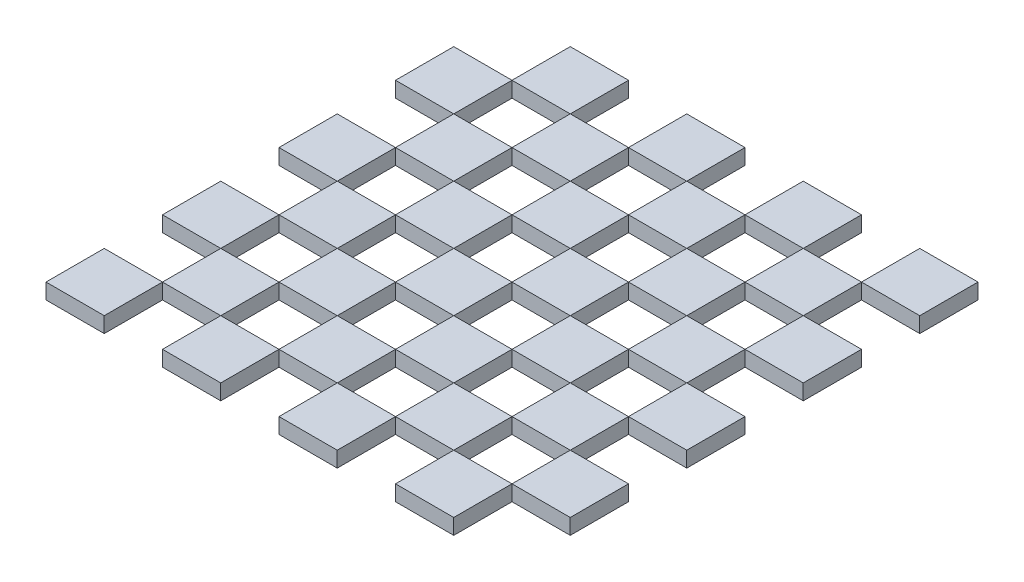
SolidWorks part; units mm, degrees
material "Plain Carbon Steel"
ref_plane "Front Plane" through (0, 0, 0) normal (0, 0, 1) x (1, 0, 0)
ref_plane "Top Plane" through (0, 0, 0) normal (0, 1, 0) x (1, 0, 0)
ref_plane "Right Plane" through (0, 0, 0) normal (1, 0, 0) x (0, 0, -1)
sketch "Sketch1" plane through (0, 0, 0) normal (0, 1, 0) x (1, 0, 0)
  line L0 (0, 150) -> (0, -150)
  line L1 (-150, -150) -> (150, -150)
  line L2 (-150, -150) -> (-150, 150)
  line L3 (-150, 150) -> (150, 150)
  line L4 (150, -150) -> (150, 150)
  line L5 (-150, -150) -> (150, 150) construction
  line L6 (-150, 150) -> (150, -150) construction
  line L7 (-112.5, 150) -> (-112.5, -150)
  line L8 (37.5, 150) -> (37.5, -150)
  line L9 (-75, 150) -> (-75, -150)
  line L10 (-37.5, 150) -> (-37.5, -150)
  line L11 (75, 150) -> (75, -150)
  line L12 (112.5, 150) -> (112.5, -150)
  line L13 (-150, -75) -> (150, -75)
  line L14 (-150, 37.5) -> (150, 37.5)
  line L15 (-150, 75) -> (150, 75)
  line L16 (-150, -112.5) -> (150, -112.5)
  line L17 (-150, 0) -> (150, 0)
  line L18 (-150, -37.5) -> (150, -37.5)
  line L19 (-150, 112.5) -> (150, 112.5)
  point P0 (0, 0)
  point P20 (0, 0)
  dimension "D1" = 300
  dimension "D2" = 37.5
  dimension "D3" = 37.5
  dimension "D4" = 37.5
  dimension "D5" = 37.5
  dimension "D6" = 37.5
  dimension "D7" = 37.5
  dimension "D8" = 37.5
  dimension "D9" = 37.5
  dimension "D10" = 37.5
  dimension "D11" = 37.5
  dimension "D12" = 37.5
  dimension "D13" = 37.5
extrude "Boss-Extrude1" add sketch "Sketch1" along normal blind 10 contours L16 L2 L1 L7 | L16 L9 L1 L10 | L16 L0 L1 L8 | L16 L11 L1 L12 | L12 L16 L4 L13 | L12 L18 L4 L17 | L15 L12 L14 L4 | L12 L19 L4 L3 | L19 L11 L15 L12 | L11 L17 L12 L14 | L18 L11 L13 L12 | L8 L16 L11 L13 | L8 L18 L11 L17 | L15 L8 L14 L11 | L8 L19 L11 L3 | L19 L0 L15 L8 | L0 L17 L8 L14 | L18 L0 L13 L8 | L10 L16 L0 L13 | L10 L18 L0 L17 | L15 L10 L14 L0 | L10 L19 L0 L3 | L7 L19 L9 L3 | L19 L2 L15 L7 | L19 L9 L15 L10 | L15 L7 L14 L9 | L9 L17 L10 L14 | L2 L17 L7 L14 | L7 L18 L9 L17 | L18 L2 L13 L7 | L18 L9 L13 L10 | L7 L16 L9 L13 region at (-18.75, 0, -131.25) region at (18.75, 0, -93.75) region at (56.25, 0, -131.25) region at (-18.75, 0, -56.25) region at (-56.25, 0, -93.75) region at (-93.75, 0, -131.25) region at (18.75, 0, -18.75) region at (56.25, 0, -56.25) region at (93.75, 0, -93.75) region at (131.25, 0, -131.25) region at (-18.75, 0, 18.75) region at (-56.25, 0, -18.75) region at (-93.75, 0, -56.25) region at (-131.25, 0, -93.75) region at (18.75, 0, 56.25) region at (56.25, 0, 18.75) region at (93.75, 0, -18.75) region at (131.25, 0, -56.25) region at (-18.75, 0, 93.75) region at (-56.25, 0, 56.25) region at (-93.75, 0, 18.75) region at (-131.25, 0, -18.75) region at (18.75, 0, 131.25) region at (56.25, 0, 93.75) region at (93.75, 0, 56.25) region at (131.25, 0, 18.75) region at (-56.25, 0, 131.25) region at (-93.75, 0, 93.75) region at (-131.25, 0, 56.25) region at (93.75, 0, 131.25) region at (131.25, 0, 93.75) region at (-131.25, 0, 131.25)
